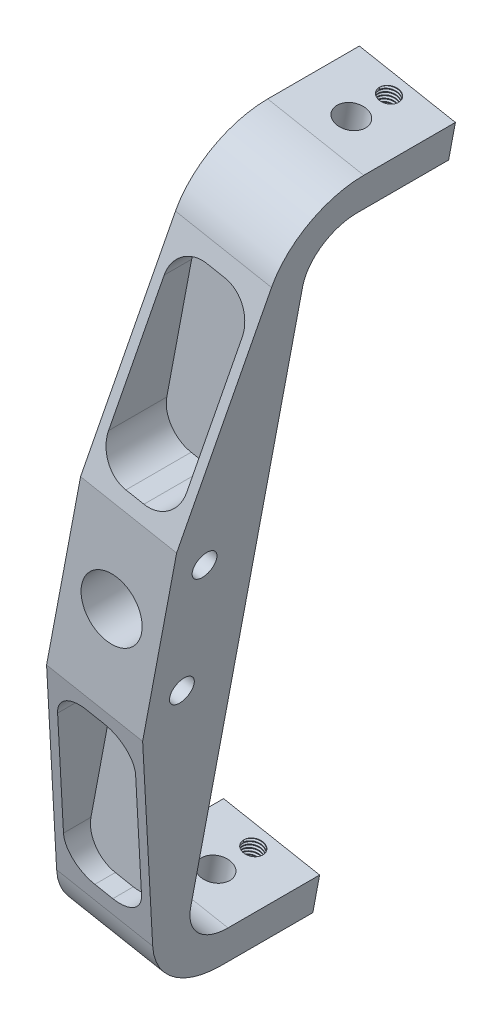
SolidWorks part; units mm, degrees
other "Markup1"
sketch "Sketch6" plane through (39.3536, 123.4271, -45) normal (0.998, 0.0328, -0.0532) x (-0.0595, 0.2351, -0.9701)
other "Markup2"
sketch "Sketch7" plane through (39.3536, 123.4271, -45) normal (0.9999, 0.0057, -0.0131) x (0.0031, -0.9818, -0.1901)
other "Markup4"
sketch "Sketch9" plane through (-39.3536, 123.4271, 27) normal (-0.9915, 0.1233, 0.0413) x (-0.1205, -0.9906, 0.0646)
other "Markup5"
sketch "Sketch12" plane through (-39.3536, 123.4271, 28.5) normal (-0.7749, 0.0474, 0.6304) x (0.632, 0.0395, 0.7739)
material "6061-T6 (SS)"
ref_plane "Front Plane" through (0, 0, 0) normal (0, 0, 1) x (1, 0, 0)
ref_plane "Top Plane" through (0, 0, 0) normal (0, 1, 0) x (1, 0, 0)
ref_plane "Right Plane" through (0, 0, 0) normal (1, 0, 0) x (0, 0, -1)
sketch "Sketch1" plane through (0, 0, 0) normal (0, 0, 1) x (1, 0, 0)
  line L0 (23.3397, 123.7002) -> (23.3397, 145.9252) construction
  line L1 (0, 0) -> (0, -276.86) construction
  line L2 (0, -276.86) -> (-52.2377, -276.86) construction
  line L3 (23.3397, 123.7002) -> (-52.2377, -276.86) construction
  line L8 (-23.3397, -123.7002) -> (-27.4603, -145.5398) construction
  line L9 (-7.6171, -126.6667) -> (39.0622, 120.7336)
  line L14 (-39.0622, -120.7336) -> (7.6171, 126.6667)
  line L17 (23.3397, 123.7002) -> (27.4603, 145.5398) construction
  line L19 (-7.6171, -126.6667) -> (-39.0622, -120.7336)
  line L20 (-23.3397, -123.7002) -> (-25.4, -134.62) construction
  line L21 (7.6171, 126.6667) -> (39.0622, 120.7336)
  line L22 (23.3397, 123.7002) -> (-23.3397, -123.7002) construction
  circle A0 centre (0, 0) radius 276.86 construction
  circle A1 centre (0, 0) radius 10
  circle A2 centre (0, 0) radius 170.5 construction
  point P4 (25.4, 134.62)
  point P6 (0, 0)
  point P10 (0, -170.5)
  point P13 (-10.5081, -129.9032)
  point P17 (0, 0)
  point P18 (41.7595, 124.248)
  point P19 (-41.8145, -123.9803)
  point P20 (10.5081, 129.9032)
  point P25 (-25.4, -134.62)
  point P31 (0, 0)
  point P32 (-23.3397, -123.7002)
  dimension "D4" = 341
  dimension "D9" = 20
  dimension "D2" = 553.72
  dimension "D3" = 22.225
  dimension "D5" = 50.8
  dimension "D6" = 32
  dimension "D7" = 52.2377
  dimension "D8" = 251.7655
  dimension "D11" = 11.1125
  dimension "D12" = 269.24
extrude "Boss-Extrude1" add sketch "Sketch1" along normal blind 28.5
sketch "Sketch2" plane through (0, 0, 0) normal (0, 0, -1) x (-1, 0, 0)
  line L0 (-36.8373, 108.9417) -> (-5.3922, 114.8748)
  line L1 (5.3922, -114.8748) -> (36.8373, -108.9417)
  line L2 (-5.3922, 114.8748) -> (-7.6171, 126.6667)
  line L3 (5.3922, -114.8748) -> (7.6171, -126.6667)
  line L4 (-7.6171, 126.6667) -> (-39.0622, 120.7336)
  line L5 (-39.0622, 120.7336) -> (7.6171, -126.6667)
  line L6 (-7.6171, 126.6667) -> (-39.0622, 120.7336)
  line L7 (39.0622, -120.7336) -> (-7.6171, 126.6667)
  line L9 (-39.0622, 120.7336) -> (-36.8373, 108.9417)
  line L11 (39.0622, -120.7336) -> (36.8373, -108.9417)
  line L14 (7.6171, -126.6667) -> (39.0622, -120.7336)
  line L15 (7.6171, -126.6667) -> (39.0622, -120.7336)
  dimension "D2" = 12
  dimension "D1" = 0
extrude "Boss-Extrude2" add sketch "Sketch2" along normal blind 45
sketch "Sketch4" plane through (-1.6562, 128.4164, 0) normal (0.1854, 0.9827, 0) x (0.9827, -0.1854, 0)
  line L0 (25.4368, -28.5) -> (25.4368, 45) construction
  line L3 (9.4368, 45) -> (41.4368, 45) construction
  line L12 (9.4368, 26.6476) -> (41.4368, 26.6476) construction
  line L13 (9.4368, -28.5) -> (9.4368, 45) construction
  line L14 (41.4368, -28.5) -> (41.4368, 45) construction
  circle A0 centre (25.4368, 26.6476) radius 4.7625
  circle A1 centre (25.4368, 39) radius 3.175
  point P6 (25.4368, 26.6476)
  dimension "D2" = 9.525
  dimension "D3" = 6.35
  dimension "D1" = 18.3524
  dimension "D4" = 6
extrude "Cut-Extrude1" cut sketch "Sketch4" against normal through all
fillet "Fillet3" radius 15 2 edges at (21.1148, 111.9082, 0) (-21.1148, -111.9082, 0)
sketch "Sketch10" plane through (-16.0243, 1.3676, 0) normal (0.9827, -0.1854, 0) x (0, 0, -1)
  line L0 (-28.5, 31.6271) -> (-11.3167, 106.5459)
  line L1 (-28.5, 31.6271) -> (-46.9127, 31.4169)
  line L2 (-46.9127, 31.4169) -> (-44.7685, 140.1716)
  line L3 (-44.7685, 140.1716) -> (15, 127.5099)
  line L4 (0, 1.6271) -> (-52.8517, 1.6271) construction
  line L5 (-28.5, 127.5099) -> (45, 127.5099) construction
  line L6 (-28.5, -124.2556) -> (-28.5, 127.5099) construction
  line L7 (-44.7685, -136.9173) -> (15, -124.2556)
  line L8 (-46.9127, -28.1627) -> (-44.7685, -136.9173)
  line L9 (-28.5, -28.3729) -> (-46.9127, -28.1627)
  line L10 (-28.5, -28.3729) -> (-11.3167, -103.2916)
  line L11 (-28.5, 31.6271) -> (0, 31.6271) construction
  line L12 (0, -97.2556) -> (0, 100.5099) construction
  line L13 (-17.5, -18.3729) -> (-17.5, 21.6271) construction
  arc A0 (15, 115.5099) -> (0, 100.5099) centre (15, 100.5099) ccw construction
  arc A1 (15, 115.5099) -> (0, 100.5099) centre (15, 100.5099) ccw construction
  arc A2 (15, 127.5099) -> (-11.3167, 106.5459) centre (15, 100.5099) ccw
  arc A3 (15, -112.2556) -> (0, -97.2556) centre (15, -97.2556) cw construction
  arc A4 (15, -124.2556) -> (-11.3167, -103.2916) centre (15, -97.2556) cw
  circle A5 centre (-17.5, 21.6271) radius 4
  circle A6 centre (-17.5, -18.3729) radius 4
  point P14 (15, 127.5099)
  point P29 (15, -124.2556)
  point P37 (-17.5, 1.6271)
  dimension "D1" = 30
  dimension "D2" = 8
  dimension "D3" = 17.5
  dimension "D4" = 40
extrude "Cut-Extrude2" cut sketch "Sketch10" against normal through all both and the other way through all
sketch "Sketch11" plane through (0, 0, 28.5) normal (0, 0, 1) x (1, 0, 0)
  line L1 (0, 0) -> (75.6649, -14.2764) construction
  line L2 (35.1753, 100.1331) -> (21.2848, 26.5133) construction
  line L3 (35.1753, 100.1331) -> (21.2848, 26.5133) construction
  line L7 (3.5413, 34.9494) -> (9.4373, 33.8369)
  line L12 (-10.1604, 32.4464) -> (3.7302, 106.0662) construction
  line L13 (-10.1604, 32.4464) -> (3.7302, 106.0662) construction
  line L15 (21.118, 41.8095) -> (29.2542, 84.9314)
  line L26 (-4.4312, 46.6301) -> (3.705, 89.752)
  line L27 (2.6111, 100.1348) -> (34.0562, 94.2018) construction
  line L39 (15.3857, 97.7245) -> (21.2816, 96.6121)
  line L40 (-21.2848, -26.5133) -> (-35.1753, -100.1331) construction
  line L41 (-3.7302, -106.0662) -> (10.1604, -32.4464) construction
  line L42 (-21.2816, -96.6121) -> (-15.3857, -97.7245)
  line L43 (-21.118, -41.8095) -> (-29.2542, -84.9314)
  line L44 (4.4312, -46.6301) -> (-3.705, -89.752)
  line L45 (-9.4373, -33.8369) -> (-3.5413, -34.9494)
  arc A0 (9.4373, 33.8369) -> (21.118, 41.8095) centre (11.2913, 43.6636) ccw
  arc A1 (3.5413, 34.9494) -> (-4.4312, 46.6301) centre (5.3954, 44.776) cw
  arc A2 (15.3857, 97.7245) -> (3.705, 89.752) centre (13.5316, 87.8979) ccw
  arc A3 (29.2542, 84.9314) -> (21.2816, 96.6121) centre (19.4275, 86.7855) ccw
  arc A4 (-3.705, -89.752) -> (-15.3857, -97.7245) centre (-13.5316, -87.8979) cw
  arc A5 (-21.2816, -96.6121) -> (-29.2542, -84.9314) centre (-19.4275, -86.7855) cw
  arc A6 (-9.4373, -33.8369) -> (-21.118, -41.8095) centre (-11.2913, -43.6636) ccw
  arc A7 (-3.5413, -34.9494) -> (4.4312, -46.6301) centre (-5.3954, -44.776) cw
  point P12 (-3.4131, 31.3285)
  point P15 (10.5274, 99.16)
  point P16 (29.4323, 95.2747)
  point P17 (15.4917, 27.4432)
  point P18 (27.5728, 26.3797)
  point P19 (-17.6556, 26.3797)
  dimension "D4" = 10
  dimension "D2" = 6
  dimension "D1" = 35
  dimension "D3" = 6
extrude "Cut-Extrude4" cut sketch "Sketch11" against normal offset from surface (22.5 mm away) 6 up to face at (10, 0, 0)
thread "Thread1" pitch 1.0583 method cut profile "Thread Profile2" start angle 0, offset 0, length 0, pitch 1.0583, diameter 6.35
ref_plane "Plane2" through (20.2197, 124.2888, -39) normal (0, 0, 1) x (-0.9827, 0.1854, 0)
sketch "Thread Profile2" plane through (20.2197, 124.2888, -39) normal (0, 0, 1) x (-0.9827, 0.1854, 0)
  line L0 (0, 0) -> (0, 1.0583) construction
  line L1 (0, 0) -> (0.5728, 0.3307)
  line L2 (0.5728, 0.3307) -> (0.5728, 0.463)
  line L3 (0.5728, 0.463) -> (0, 0.7937)
  line L4 (0.5728, 0.3969) -> (0, 0.3969) construction
  line L11 (0, 0) -> (0, 0.7937)
  point P2 (0, 0)
  dimension "Pitch" = 1.0583
  dimension "Profile_Angle" = 60
  dimension "Profile_Land" = 0.1323
  dimension "Profile_Height" = 0.5728
thread "Thread2" pitch 1.0583 method cut profile "Thread Profile3" start angle 0, offset 0, length 0, pitch 1.0583, diameter 6.35
ref_plane "Plane3" through (-24.2347, -111.3196, -39) normal (0, 0, 1) x (-0.9827, 0.1854, 0)
sketch "Thread Profile3" plane through (-24.2347, -111.3196, -39) normal (0, 0, 1) x (-0.9827, 0.1854, 0)
  line L0 (0, 0) -> (0, 1.0583) construction
  line L1 (0, 0) -> (0.5728, 0.3307)
  line L2 (0.5728, 0.3307) -> (0.5728, 0.463)
  line L3 (0.5728, 0.463) -> (0, 0.7937)
  line L4 (0.5728, 0.3969) -> (0, 0.3969) construction
  line L11 (0, 0) -> (0, 0.7937)
  point P2 (0, 0)
  dimension "Pitch" = 1.0583
  dimension "Profile_Angle" = 60
  dimension "Profile_Land" = 0.1323
  dimension "Profile_Height" = 0.5728
